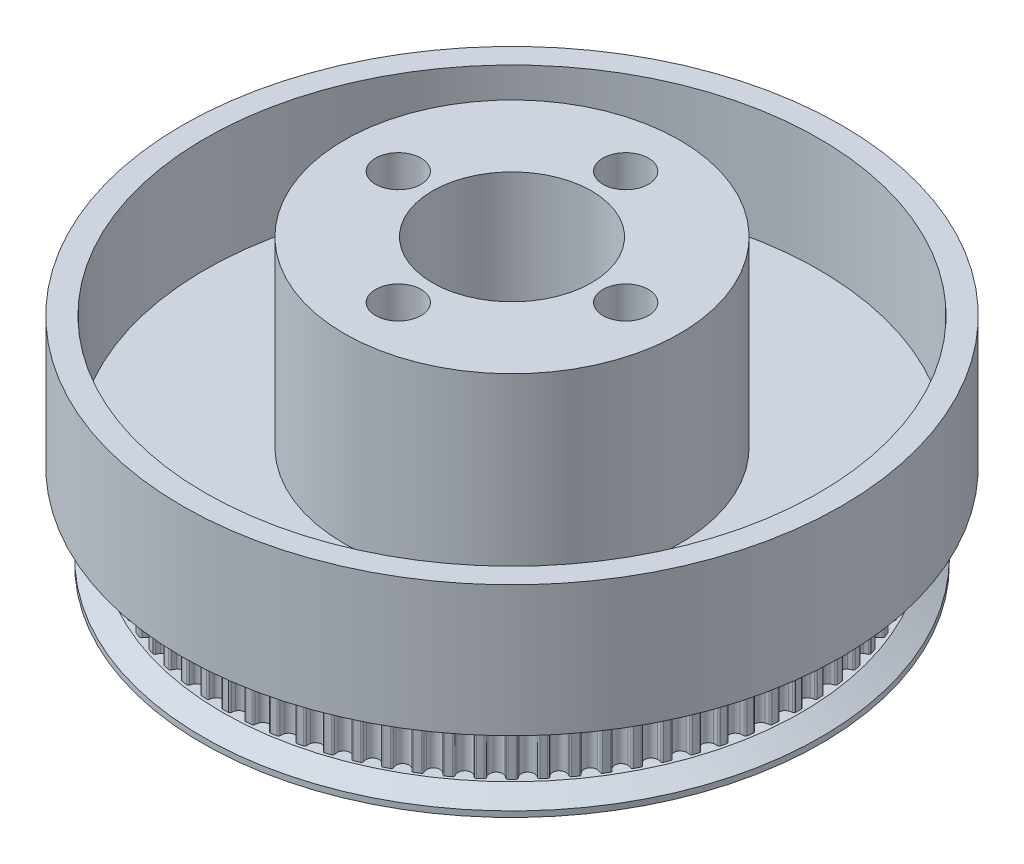
SolidWorks part; units mm, degrees
ref_plane "Front" through (0, 0, 0) normal (0, 0, 1) x (1, 0, 0)
ref_plane "Top" through (0, 0, 0) normal (0, 1, 0) x (1, 0, 0)
ref_plane "Right" through (0, 0, 0) normal (1, 0, 0) x (0, 0, -1)
sketch "Sketch1" plane through (0, 0, 0) normal (0, 1, 0) x (1, 0, 0)
  line L0 (0, 0) -> (0, 25.4648) construction
  line L1 (0, 25.2108) -> (0, 25.8408)
  line L2 (0, 0) -> (0.9997, 25.4452) construction
  line L3 (1.978, 25.1331) -> (2.0274, 25.7611)
  line L4 (1.3894, 25.1757) -> (1.4033, 25.4261) construction
  arc A0 (0.2468, 25.2096) -> (0.3946, 25.0747) centre (0.2453, 25.0596) cw
  arc A1 (0.3946, 25.0747) -> (0.4741, 24.773) centre (1.3894, 25.1757) ccw
  circle A2 centre (0, 0) radius 25.4648 construction
  arc A3 (0.2468, 25.2096) -> (0, 25.2108) centre (0, 0) ccw
  arc A4 (0.9603, 24.4419) -> (0, 24.4608) centre (0, 0) ccw construction
  arc A5 (0.4741, 24.773) -> (1.471, 24.7339) centre (0.9821, 24.9965) ccw
  arc A6 (1.3894, 25.1757) -> (0.9899, 25.1946) centre (0, 0) ccw construction
  arc A7 (0, 25.8408) -> (2.0274, 25.7611) centre (0, 0) cw
  arc A8 (1.574, 25.0284) -> (1.471, 24.7339) centre (0.5901, 25.2071) cw
  arc A9 (1.7319, 25.1512) -> (1.574, 25.0284) centre (1.7216, 25.0016) ccw
  arc A10 (1.7319, 25.1512) -> (1.978, 25.1331) centre (0, 0) cw
  dimension "D1" = 0.15
  dimension "D4" = 50.9296
  dimension "D5" = 1
  dimension "D7" = 0.555
  dimension "D3" = 2.25
  dimension "D8" = 0.75
  dimension "D6" = 0.254
  dimension "D2" = 0.4
  dimension "D9" = 1.38
  dimension "D11" = 0.404
  dimension "D12" = 0.2508
  dimension "D10" = 0.909
sketch "Sketch2" plane through (0, 0, 0) normal (0, 1, 0) x (1, 0, 0)
  circle A0 centre (0, 0) radius 25.4648 construction
  circle A1 centre (0, 0) radius 25.4648
  circle A2 centre (0, 0) radius 7
  dimension "D1" = 14
extrude "Boss-Extrude1" add sketch "Sketch2" along normal mid plane 6
sketch "Sketch6" plane through (0, 0, 0) normal (0, 1, 0) x (1, 0, 0)
  line L0 (0, 25.2008) -> (0, 25.8408)
  line L1 (1.9772, 25.1231) -> (2.0274, 25.7611)
  arc A7 (2.0274, 25.7611) -> (0, 25.8408) centre (0, 0) ccw construction
  arc A8 (2.0274, 25.7611) -> (0, 25.8408) centre (0, 0) ccw
  arc A14 (1.7312, 25.1413) -> (1.5838, 25.0266) centre (1.7216, 25.0016) ccw
  arc A15 (1.4798, 24.7291) -> (1.5838, 25.0266) centre (0.5901, 25.2071) ccw
  arc A16 (0.4649, 24.769) -> (1.4798, 24.7291) centre (0.9821, 24.9965) ccw
  arc A17 (0.3846, 25.0737) -> (0.4649, 24.769) centre (1.3894, 25.1757) ccw
  arc A18 (0.3846, 25.0737) -> (0.2467, 25.1996) centre (0.2453, 25.0596) ccw
  arc A19 (0.2467, 25.1996) -> (0, 25.2008) centre (0, 0) ccw
  arc A20 (1.9772, 25.1231) -> (1.7312, 25.1413) centre (0, 0) ccw
  arc A21 (1.7312, 25.1413) -> (1.5838, 25.0266) centre (1.7216, 25.0016) ccw
  arc A22 (1.4798, 24.7291) -> (1.5838, 25.0266) centre (0.5901, 25.2071) ccw
  arc A23 (0.4649, 24.769) -> (1.4798, 24.7291) centre (0.9821, 24.9965) ccw
  arc A24 (0.3846, 25.0737) -> (0.4649, 24.769) centre (1.3894, 25.1757) ccw
  arc A25 (0.3846, 25.0737) -> (0.2467, 25.1996) centre (0.2453, 25.0596) ccw
  arc A26 (0.2467, 25.1996) -> (0, 25.2008) centre (0, 0) ccw
  arc A27 (1.9772, 25.1231) -> (1.7312, 25.1413) centre (0, 0) ccw
extrude "Cut-Extrude3" cut sketch "Sketch6" against normal through all both and the other way through all
pattern_circular "CirPattern3" count 80 over 360 about axis through (0, 3, 0) along (0, -1, 0) of "Cut-Extrude3"
sketch "Sketch3" plane through (0, 0, 0) normal (0, 0, 1) x (1, 0, 0)
  line L0 (0, 0) -> (0, 9.5108) construction
  line L1 (-25.4648, 3) -> (-27.1968, 4)
  line L2 (-27.1968, 4) -> (-27.1968, 4.5)
  line L3 (-27.1968, 4.5) -> (-7, 4.5)
  line L4 (-7, 4.5) -> (-7, 3)
  line L5 (-7, 3) -> (-25.4648, 3)
  line L6 (7, 3) -> (-7, 3) construction
  dimension "D4" = 50.9296
  dimension "D1" = 1.5
  dimension "D2" = 0.5
  dimension "D3" = 30
revolve "Revolve1" add sketch "Sketch3" angle 360 about L0
mirror "Mirror1" about plane through (0, 0, 0) normal (0, 1, 0) of "Revolve1"
sketch "Sketch4" plane through (0, 0, 0) normal (0, 0, 1) x (1, 0, 0)
  line L0 (0, 0) -> (0, 14.0175) construction
  line L1 (27.1968, 4.5) -> (-27.1968, 4.5) construction
  line L2 (-7, 4.5) -> (-13.5, 4.5)
  line L3 (-7, 4.5) -> (-7, 10.5)
  line L4 (-7, 10.5) -> (-13.5, 10.5)
  line L5 (-13.5, 4.5) -> (-13.5, 10.5)
  dimension "D2" = 6
  dimension "D1" = 6.5
revolve "Revolve2" add sketch "Sketch4" angle 360 about L0
sketch "Sketch5" plane through (0, 0, 0) normal (0, 0, 1) x (1, 0, 0)
  line L1 (0, 4.5) -> (0, 10.5) construction
  line L2 (13.5, 10.5) -> (-13.5, 10.5) construction
  line L7 (-13.5, 10.5) -> (-13.5, 4.5) construction
  line L8 (-13.5, 10.5) -> (-13.5, 4.5) construction
  circle A0 centre (0, 7.5) radius 1.6
  dimension "D1" = 3.2
extrude "Cut-Extrude2" cut sketch "Sketch5" along normal through all
pattern_circular "CirPattern2" count 2 over 90 about axis through (0, 3, 0) along (0, -1, 0) of "Cut-Extrude2" reverse direction yes
sketch "Esboço1" plane through (0, 4.5, 0) normal (0, 1, 0) x (1, 0, 0)
  circle A0 centre (0, 0) radius 14.75
  circle A1 centre (0, 10) radius 1.5823
  circle A2 centre (0, 0) radius 7
  circle A3 centre (10, 0) radius 1.5823
  circle A4 centre (0, -10) radius 1.5823
  circle A5 centre (-10, 0) radius 1.5823
  point P15 (0, 0)
  dimension "D1" = 29.5
  dimension "D2" = 10
  dimension "D3" = 14
  dimension "D4" = 4
extrude "Ressalto-extrusão1" add sketch "Esboço1" along normal blind 16
sketch "Esboço3" plane through (0, 3, 0) normal (0, -1, 0) x (1, 0, 0)
  circle A0 centre (0, 0) radius 26 construction
  circle A1 centre (0, 0) radius 29
  circle A2 centre (0, 0) radius 7
  dimension "D1" = 52
  dimension "D2" = 58
extrude "Ressalto-extrusão2" add sketch "Esboço3" against normal up to surface (1.5 mm away) up to face at (0, 4.5, -14.75)
sketch "Esboço4" plane through (0, 4.5, 0) normal (0, 1, 0) x (1, 0, 0)
  circle A0 centre (0, 0) radius 29
  circle A1 centre (0, 0) radius 27
  dimension "D1" = 54
extrude "Ressalto-extrusão3" add sketch "Esboço4" along normal blind 10
sketch "Esboço2" plane through (0, 20.5, 0) normal (0, 1, 0) x (1, 0, 0)
  circle A0 centre (0, 10) radius 2
  circle A1 centre (10, 0) radius 2
  circle A2 centre (0, -10) radius 2
  circle A3 centre (-10, 0) radius 2
  point P12 (0, 0)
  dimension "D2" = 4
  dimension "D1" = 4
extrude "Corte-extrusão1" cut sketch "Esboço2" against normal through all
equation "\"belt-step\"= 2"
equation "\"pulley-teeth\"= 80"
equation "\"pulley-dia\"= ( \"belt-step\" * \"pulley-teeth\" ) / Pi"
equation "\"D3@Sketch1\"=(360/\"pulley-teeth\")/2"
equation "\"D4@Sketch1\"=\"pulley-dia\""
equation "\"bore-dia\"= 14"
equation "\"belt-thick\"= 6"
equation "\"D4@Sketch3\"=\"pulley-dia\""
equation "\"D1@Sketch2\"=\"bore-dia\""
equation "\"D1@Boss-Extrude1\"=\"belt-thick\""
equation "\"teeth-offset\"= 0.01"
equation "\"D1@Sketch6\"=\"teeth-offset\""
equation "\"D1@CirPattern3\"=\"pulley-teeth\""
equation "\"flange-wall\"= 6.5"
equation "\"D1@Sketch4\"=\"flange-wall\""
equation "\"flange-h\"= 6"
equation "\"screw-dia\"= 3.2"
equation "\"D2@Sketch4\"=\"flange-h\""
equation "\"D1@Sketch5\"=\"screw-dia\""
equation "\"D10@Sketch1\"=(0.4/(Pi*(\"pulley-dia\"-(2*\"D12@Sketch1\"))))*360"
